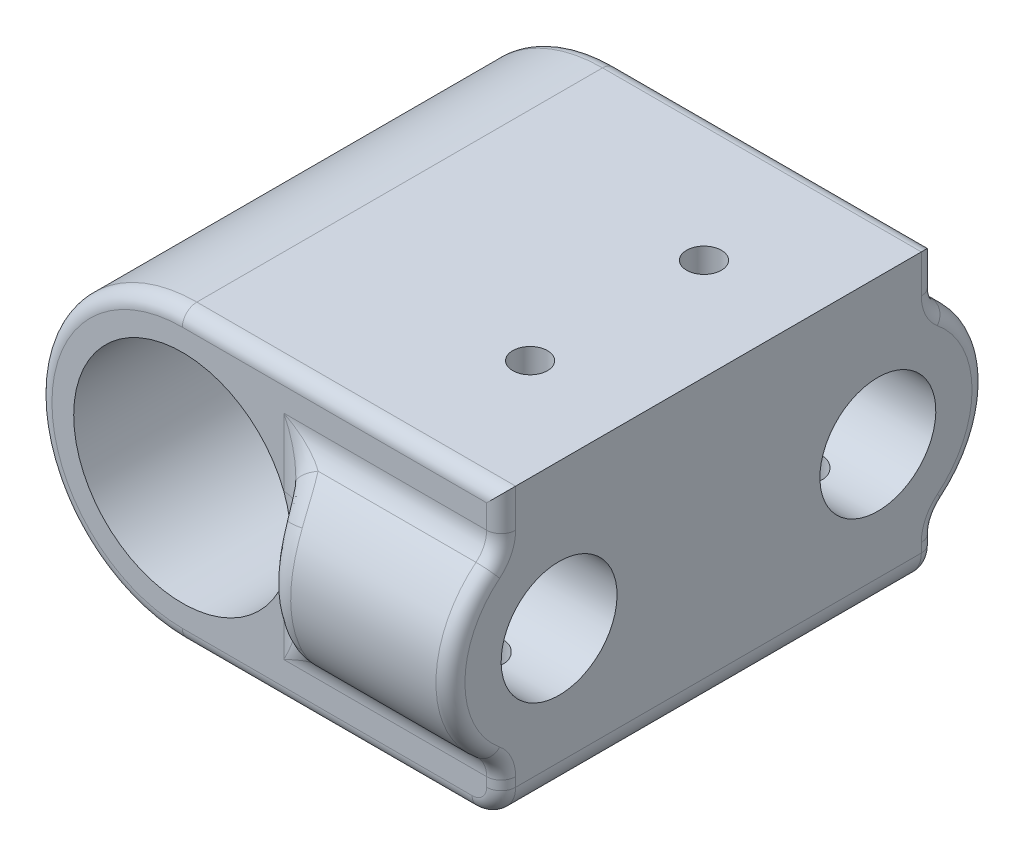
SolidWorks part; units mm, degrees
ref_plane "Front" through (0, 0, 0) normal (0, 0, 1) x (1, 0, 0)
ref_plane "Top" through (0, 0, 0) normal (0, 1, 0) x (1, 0, 0)
ref_plane "Right" through (0, 0, 0) normal (1, 0, 0) x (0, 0, -1)
sketch "Эскиз1" plane through (0, 0, 0) normal (0, 0, 1) x (1, 0, 0)
  line L1 (0, 10) -> (22, 10)
  line L3 (0, -10) -> (20, -10)
  line L4 (22, 10) -> (22, -8)
  circle A0 centre (0, 0) radius 7.5
  arc A1 (0, 10) -> (0, -10) centre (0, 0) ccw
  arc A2 (20, -10) -> (22, -8) centre (20, -8) ccw
  point P11 (22, 10)
  dimension "D1" = 15
  dimension "D2" = 20
  dimension "D4" = 2
  dimension "D6" = 10
  dimension "D3" = 22
extrude "Бобышка-Вытянуть1" add sketch "Эскиз1" along normal blind 30
sketch "Эскиз2" plane through (22, 0, 0) normal (1, 0, 0) x (0, 0, -1)
  line L0 (-30, 0) -> (0, 0) construction
  line L1 (-30, -8) -> (-30, 10) construction
  line L2 (0, -8) -> (0, 10) construction
  line L3 (-30, 10) -> (0, 10) construction
  circle A0 centre (-26, 0) radius 4 construction
  circle A1 centre (-4, 0) radius 4 construction
  circle A2 centre (-4, 0) radius 7.5
  circle A3 centre (-26, 0) radius 7.5
  dimension "D2" = 22
  dimension "D1" = 10
  dimension "D3" = 4
  dimension "D4" = 4
extrude "Бобышка-Вытянуть2" add sketch "Эскиз2" against normal blind 13
sketch "Эскиз3" plane through (22, 0, 0) normal (1, 0, 0) x (0, 0, -1)
  circle A0 centre (-26, 0) radius 4
  circle A1 centre (-4, 0) radius 4
extrude "Вырез-Вытянуть1" cut sketch "Эскиз3" against normal blind 12
fillet "Скругление1" radius 2 6 edges at (15.5, -6.3443, 0) (15.5, 6.3443, 0) (9, 0, 0) (15.5, -6.3443, 30) (15.5, 6.3443, 30) (9, 0, 30)
fillet "Скругление2" radius 1 18 edges at (22, 6.5071, 30.1936) (22, 0, 33.5) (22, -6.5071, 30.1936) (21.4142, -9.4142, 30) (10, -10, 30) (-10, 0, 30) (22, 6.5071, -0.1936) (22, 0, -3.5) (22, -6.5071, -0.1936) (21.4142, -9.4142, 0) (10, -10, 0) (-10, 0, 0) (11, 10, 30) (11, 10, 0) (22, -7.6827, 30) (22, -7.6827, 0) (22, 8.6827, 30) (22, 8.6827, 0)
fillet "Скругление3" radius 2 10 edges at (7.8584, -6.5071, -0.1936) (8.9187, -5.1678, -1.4354) (7.8584, 6.5071, -0.1936) (8.8246, 5.4229, -1.181) (7.8584, 6.5071, 30.1936) (8.9187, 5.1678, 31.4354) (7.8584, -6.5071, 30.1936) (8.8246, -5.4229, 31.181) (9, 0, -3.5) (9, 0, 33.5)
sketch "Эскиз4" plane through (0, 10, 0) normal (0, 1, 0) x (1, 0, 0)
  line L0 (15, -1) -> (15, -29) construction
  line L1 (22, -1) -> (0, -1) construction
  line L2 (0, -29) -> (22, -29) construction
  line L3 (22, -29) -> (22, -1) construction
  circle A0 centre (15, -9) radius 1.2
  circle A1 centre (15, -21) radius 1.2
  dimension "D2" = 8
  dimension "D1" = 7
  dimension "D3" = 8
extrude "Вырез-Вытянуть2" cut sketch "Эскиз4" against normal blind 8.7
sketch "Эскиз7" plane through (0, -10, 0) normal (0, -1, 0) x (1, 0, 0)
  line L0 (17, 29) -> (17, 1) construction
  line L1 (20, 29) -> (0, 29) construction
  line L2 (0, 1) -> (20, 1) construction
  line L3 (20, 29) -> (20, 1) construction
  circle A0 centre (17, 26) radius 1.2
  circle A1 centre (17, 4) radius 1.2
  dimension "D2" = 3
  dimension "D3" = 3
  dimension "D1" = 3
extrude "Вырез-Вытянуть3" cut sketch "Эскиз7" against normal up to next
